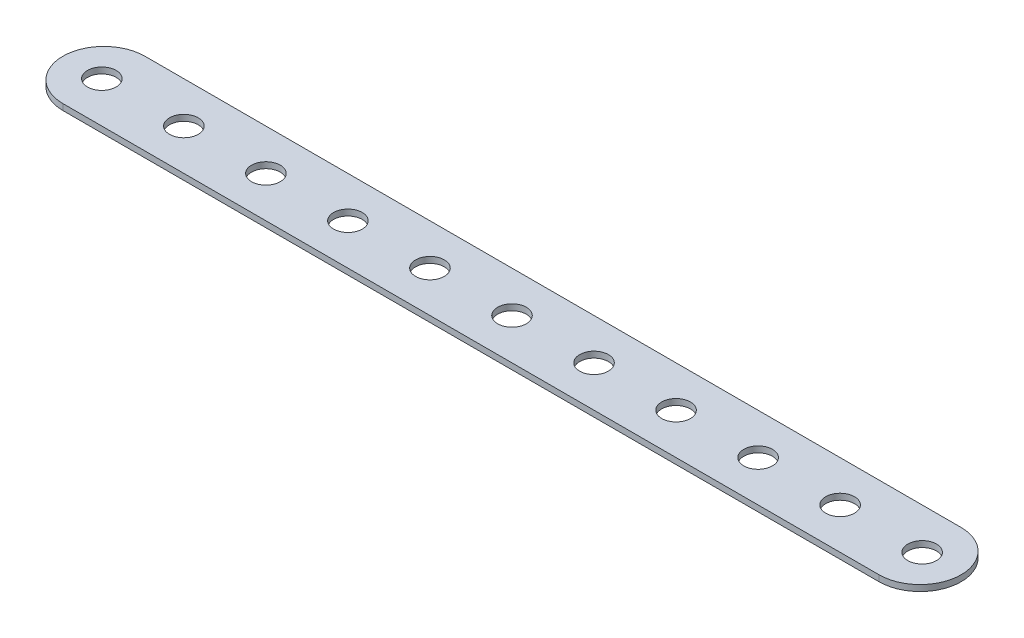
SolidWorks part; units mm, degrees
note: '?' marks a value the reader was unsure of.
material "Custom Plastic"
ref_plane "Front Plane" through (0, 0, 0) normal (0, 0, 1) x (1, 0, 0)
ref_plane "Top Plane" through (0, 0, 0) normal (0, 1, 0) x (1, 0, 0)
ref_plane "Right Plane" through (0, 0, 0) normal (1, 0, 0) x (0, 0, -1)
ref_plane "Plane1"
sketch "Sketch1" plane through (0, 0, 0) normal (0, 1, 0) x (-1, 0, 0)
  line L0 (126.365, 6.35) -> (0, 6.35)
  line L1 (0, -6.35) -> (126.365, -6.35)
  arc A0 (126.365, -6.35) -> (126.365, 6.35) centre (126.365, 0) ccw
  arc A1 (0, 6.35) -> (0, -6.35) centre (0, 0) ccw
  circle A2 centre (-0.3175, 0) radius 2.2225
  circle A3 centre (126.6825, 0) radius 2.2225
  dimension "D1" = 12.7
  dimension "D3" = 4.445
  dimension "D2" = 126.365
  dimension "D4" = 127
extrude "Bar" add sketch "Sketch1" along normal blind 0.9398 contours L0 A1 L1 A0 A3 A2
ref_plane "Plane2" through (0, 0.9398, 0) normal (0, 1, 0) x (1, 0, 0)
sketch "Sketch2" plane through (0, 0.9398, 0) normal (0, 1, 0) x (1, 0, 0)
  circle A0 centre (-113.9825, 0) radius 2.2225
  dimension "D1" = 12.3825
extrude "Center Hole" cut sketch "Sketch2" against normal through all
ref_plane "Plane3" through (0, 0, 0) normal (0, -1, 0) x (-1, 0, 0)
ref_plane "Plane4" through (0, 0, 0) normal (0, 0, 1) x (1, 0, 0)
ref_axis "Axis1" through (-80.9, 0, 0) along (1, 0, 0)?
pattern_linear "Other Center Holes" count 9 spacing 12.7 along (1, 0, 0) of "Center Hole"
